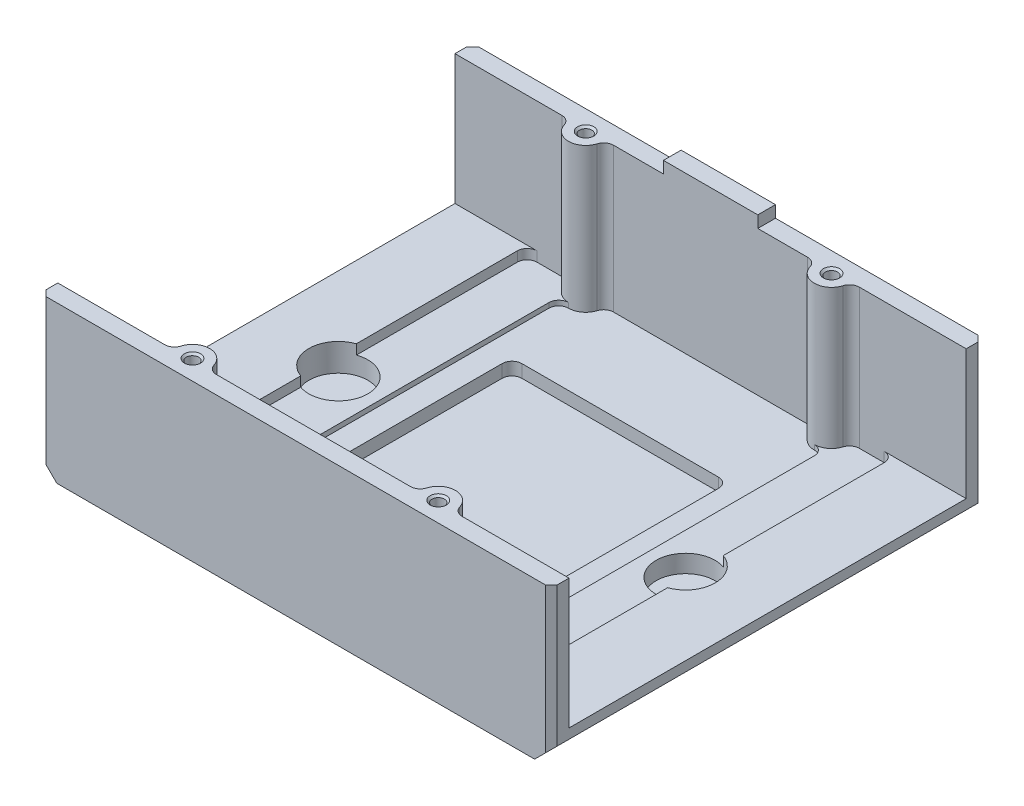
SolidWorks part; units mm, degrees
material "6061-T6 (SS)"
ref_plane "정면" through (0, 0, 0) normal (0, 0, 1) x (1, 0, 0)
ref_plane "윗면" through (0, 0, 0) normal (0, 1, 0) x (1, 0, 0)
ref_plane "우측면" through (0, 0, 0) normal (1, 0, 0) x (0, 0, -1)
sketch "스케치1" plane through (0, 0, 0) normal (0, 1, 0) x (1, 0, 0)
  line L4 (25, 42) -> (25, 40.2)
  line L6 (46, 32.8) -> (46, 41.4)
  line L7 (-5.4, -2) -> (45.4, -2) construction
  line L8 (45.4, 42) -> (25, 42)
  line L9 (46, 42) -> (-6, 42)
  line L10 (-6, -2) -> (46, -2)
  line L11 (-6, -2) -> (-6, 42)
  line L16 (46, 42) -> (46, -2)
  line L24 (40.2, 32.8) -> (46, 32.8)
  line L26 (40.2, 39.2) -> (40.2, 32.8)
  line L28 (25, 40.2) -> (31.6225, 40.2)
  line L36 (33.3775, 40.2) -> (39.2, 40.2)
  line L93 (46, 41.4) -> (45.4, 42)
  line L95 (-6, -1.4) -> (-6, 41.4) construction
  line L96 (46, 41.4) -> (46, -1.4) construction
  arc A5 (40.2, 39.2) -> (40.195, 39.3) centre (39.2, 39.2) ccw
  arc A8 (33.3775, 40.2) -> (31.6225, 40.2) centre (32.5, 40) ccw
  arc A14 (40.195, 39.3) -> (39.3, 40.195) centre (40.2, 40.2) ccw
  arc A16 (39.3, 40.195) -> (39.2, 40.2) centre (39.2, 39.2) ccw
  dimension "D1" = 0
extrude "보스-돌출1" add sketch "스케치1" against normal blind 16.5
shell "쉘1" thickness 1.8
sketch "스케치3" plane through (-4.2, 0, 0) normal (1, 0, 0) x (0, 0, -1)
  line L4 (40.2, 0) -> (-0.2, 0)
  line L5 (-0.2, 0) -> (-0.2, -14.7)
  line L6 (-0.2, -14.7) -> (40.2, -14.7)
  line L7 (40.2, -14.7) -> (40.2, 0)
  line L8 (40.2, 0) -> (-0.2, 0)
  line L9 (-0.2, 0) -> (-0.2, -14.7)
  line L10 (-0.2, -14.7) -> (40.2, -14.7)
  line L11 (40.2, -14.7) -> (40.2, 0)
  dimension "D1" = 0
extrude "컷-돌출1" cut sketch "스케치3" against normal through all both and the other way through all
sketch "스케치4" plane through (0, -14.7, 0) normal (0, 1, 0) x (1, 0, 0)
  line L1 (46, -0.2) -> (33.5, -0.2)
  line L2 (46, -0.2) -> (46, 40.2)
  line L3 (46, 40.2) -> (33.5, 40.2)
  line L4 (33.5, -0.2) -> (33.5, 40.2)
  line L5 (46, -0.2) -> (46, 40.2) construction
  line L6 (-6, -0.2) -> (6.5, -0.2)
  line L7 (-6, -0.2) -> (-6, 40.2)
  line L8 (-6, 40.2) -> (6.5, 40.2)
  line L9 (6.5, -0.2) -> (6.5, 40.2)
  line L10 (46, 40.2) -> (-6, 40.2) construction
  dimension "D1" = 12.5
  dimension "D2" = 12.5
extrude "보스-돌출2" add sketch "스케치4" along normal blind 1.5
sketch "스케치5" plane through (0, -13.2, 0) normal (0, 1, 0) x (1, 0, 0)
  line L0 (2.54, 0) -> (2.54, 40) construction
  line L1 (2.54, 40) -> (4.14, 40) construction
  line L2 (4.14, 40) -> (4.14, 0) construction
  line L3 (4.14, 0) -> (2.54, 0) construction
  line L4 (35.86, 0) -> (35.86, 40) construction
  line L5 (35.86, 40) -> (37.46, 40) construction
  line L6 (37.46, 40) -> (37.46, 0) construction
  line L7 (37.46, 0) -> (35.86, 0) construction
  line L8 (2.54, 0) -> (2.54, 40) construction
  line L9 (2.54, 40) -> (4.14, 40) construction
  line L10 (4.14, 40) -> (4.14, 0) construction
  line L11 (4.14, 0) -> (2.54, 0) construction
  line L12 (35.86, 0) -> (35.86, 40) construction
  line L13 (35.86, 40) -> (37.46, 40) construction
  line L14 (37.46, 40) -> (37.46, 0) construction
  line L15 (37.46, 0) -> (35.86, 0) construction
  line L16 (2.34, -0.2) -> (1.34, -0.2)
  line L17 (2.34, 40.2) -> (4.34, 40.2)
  line L18 (4.34, 40.2) -> (9.34, 40.2)
  line L19 (4.34, -0.2) -> (2.34, -0.2)
  line L20 (4.34, -0.2) -> (9.34, -0.2)
  line L21 (35.66, 40.2) -> (37.66, 40.2)
  line L22 (1.34, -0.2) -> (1.34, 40.2)
  line L23 (37.66, -0.2) -> (35.66, -0.2)
  line L24 (4.34, 40.2) -> (4.34, -0.2) construction
  line L25 (35.66, -0.2) -> (35.66, 40.2) construction
  line L26 (9.34, -0.2) -> (9.34, 40.2)
  line L27 (35.66, -0.2) -> (30.66, -0.2)
  line L28 (35.66, 40.2) -> (30.66, 40.2)
  line L29 (30.66, 40.2) -> (30.66, -0.2)
  line L30 (2.34, 40.2) -> (1.34, 40.2)
  line L31 (2.34, -0.2) -> (2.34, 40.2) construction
  line L32 (37.66, 40.2) -> (37.66, -0.2) construction
  line L34 (37.66, -0.2) -> (38.66, -0.2)
  line L35 (38.66, -0.2) -> (38.66, 40.2)
  line L37 (38.66, 40.2) -> (37.66, 40.2)
  dimension "D2" = 1
  dimension "D3" = 1
  dimension "D4" = 5
  dimension "D5" = 5
  dimension "D1" = 0.2
extrude "컷-돌출2" cut sketch "스케치5" against normal blind 1
sketch "스케치6" plane through (0, 0, 0) normal (0, 1, 0) x (1, 0, 0)
  circle A0 centre (7.5, 0) radius 0.75 construction
  circle A1 centre (7.5, 40) radius 0.75 construction
  circle A2 centre (32.5, 40) radius 0.75 construction
  circle A3 centre (32.5, 0) radius 0.75 construction
  circle A4 centre (7.5, 0) radius 1.75
  circle A5 centre (7.5, 40) radius 1.75
  circle A6 centre (32.5, 40) radius 1.75
  circle A7 centre (32.5, 0) radius 1.75
  dimension "D4" = 1.5
  dimension "D1" = 7.5
  dimension "D2" = 25
  dimension "D3" = 40
  dimension "D5" = 1
extrude "보스-돌출3" add sketch "스케치6" against normal up to next
hole_wizard "M1.6 나사 구멍1" positions "스케치8" profile "스케치10" tap size "M1.6" standard "ISO"
sketch "스케치8" plane through (0, 0, 0) normal (0, 1, 0) x (1, 0, 0)
  point P0 (7.5, 0)
  point P3 (32.5, 0)
  point P6 (7.5, 40)
  point P9 (32.5, 40)
cosmetic thread "구멍 나사산5" parameters "D1"=10, "D2"=1.6
cosmetic thread "구멍 나사산6" parameters "D1"=10, "D2"=1.6
cosmetic thread "구멍 나사산7" parameters "D1"=10, "D2"=1.6
cosmetic thread "구멍 나사산8" parameters "D1"=10, "D2"=1.6
sketch "스케치10" plane through (7.5, 0, 0) normal (1, 0, 0) x (0, 0, 1)
  line L0 (0, 0) -> (0, 12.3755)
  line L1 (0, 12.3755) -> (0.625, 12)
  line L2 (0.625, 12) -> (0.625, 0.2)
  line L3 (0.625, 0.2) -> (0.825, 0)
  line L5 (0.825, 0) -> (0, 0)
  line L6 (-0.625, 0.2) -> (-0.825, 0) construction
  line L10 (0, 12.3755) -> (-0.625, 12) construction
  line L11 (0, -6.35) -> (0, 107.95) construction
  dimension "탭 드릴 지름" = 1.25
  dimension "탭 드릴 깊이" = 12
  dimension "표면 카운터싱크 지름" = 1.65
  dimension "표면 카운터싱크 각도" = 90
  dimension "드릴 각도" = 118
sketch "스케치11" plane through (0, -14.7, 0) normal (0, 1, 0) x (1, 0, 0)
  line L1 (9, 9) -> (31, 9)
  line L2 (9, 9) -> (9, 31)
  line L3 (9, 31) -> (31, 31)
  line L4 (31, 9) -> (31, 31)
  point P5 (0, 0)
  dimension "D1" = 22
  dimension "D2" = 22
  dimension "D3" = 9
  dimension "D4" = 9
extrude "컷-돌출3" cut sketch "스케치11" against normal blind 1.3
sketch "스케치12" plane through (0, -16.5, 0) normal (0, -1, 0) x (1, 0, 0)
  line L1 (-6, 2) -> (4, 2)
  line L2 (-6, 2) -> (-6, -42)
  line L3 (-6, -42) -> (4, -42)
  line L4 (4, 2) -> (4, -42)
  line L5 (46, -42) -> (-6, -42) construction
  line L6 (46, 2) -> (36, 2)
  line L7 (46, 2) -> (46, -42)
  line L8 (46, -42) -> (36, -42)
  line L9 (36, 2) -> (36, -42)
  dimension "D1" = 10
  dimension "D2" = 10
extrude "컷-돌출4" [suppressed] cut sketch "스케치12" against normal blind 1.5
chamfer "모따기2" distance 0.6 angle 45 8 edges at (20, -16.5, -42) (20, -16.5, 2) (46, -8.25, -42) (46, -16.5, -20) (46, -8.25, 2) (-6, -8.25, -42) (-6, -16.5, -20) (-6, -8.25, 2)
fillet "필렛1" radius 1 20 edges at (38.66, -13.7, 0.2) (38.66, -13.7, -40.2) (9.2385, -7.35, 0.2) (6.5, -14.45, -1.4361) (5.7615, -7.1, 0.2) (5.7615, -7.1, -40.2) (6.5, -14.45, -38.5639) (9.2385, -7.35, -40.2) (30.7615, -7.35, -40.2) (33.5, -14.45, -38.5639) (34.2385, -7.1, -40.2) (34.2385, -7.1, 0.2) (33.5, -14.45, -1.4361) (30.7615, -7.35, 0.2) (9, -15.35, -9) (9, -15.35, -31) (31, -15.35, -31) (31, -15.35, -9) (1.34, -13.7, -40.2) (1.34, -13.7, 0.2)
sketch "스케치13" plane through (0, 0, 0) normal (0, 1, 0) x (1, 0, 0)
  line L0 (29.8689, 40.2) -> (10.1311, 40.2) construction
  line L1 (24.8, 40.2) -> (15.2, 40.2)
  line L2 (24.8, 40.2) -> (24.8, 42)
  line L3 (24.8, 42) -> (15.2, 42)
  line L4 (15.2, 40.2) -> (15.2, 42)
  line L5 (45.4, 42) -> (-5.4, 42) construction
  line L6 (25, 42) -> (25, 40.2) construction
  line L7 (15, 40.2) -> (15, 42) construction
  point P10 (25, 41.1)
  dimension "D1" = 0.2
  dimension "D2" = 0.2
extrude "보스-돌출4" add sketch "스케치13" along normal blind 1.2
chamfer "모따기3" distance 2.3 angle 45 2 edges at (46, -16.5, -20) (-6, -16.5, -20)
sketch "스케치14" plane through (0, 0, 0) normal (0, 1, 0) x (1, 0, 0)
  line L0 (-13.4417, 20) -> (54.3497, 20) construction
  line L1 (2.34, 40.2) -> (2.34, -0.2) construction
  line L2 (37.66, 40.2) -> (37.66, -0.2) construction
  line L3 (20, 31) -> (20, 9) construction
  line L4 (30, 31) -> (10, 31) construction
  line L5 (10, 9) -> (30, 9) construction
  line L7 (37.66, 40.2) -> (35.1311, 40.2) construction
  circle A0 centre (2.34, 20) radius 3
  circle A1 centre (37.66, 20) radius 3
  arc A2 (38.66, 39.2) -> (37.66, 40.2) centre (37.66, 39.2) ccw construction
  point P14 (20, 20)
  dimension "D1" = 6
extrude "컷-돌출5" cut sketch "스케치14" against normal offset from surface (16 mm away) 0.5 up to face at (20, -16.5, -20)
equation "\"D2@스케치4\"=\"D1@스케치4\""
